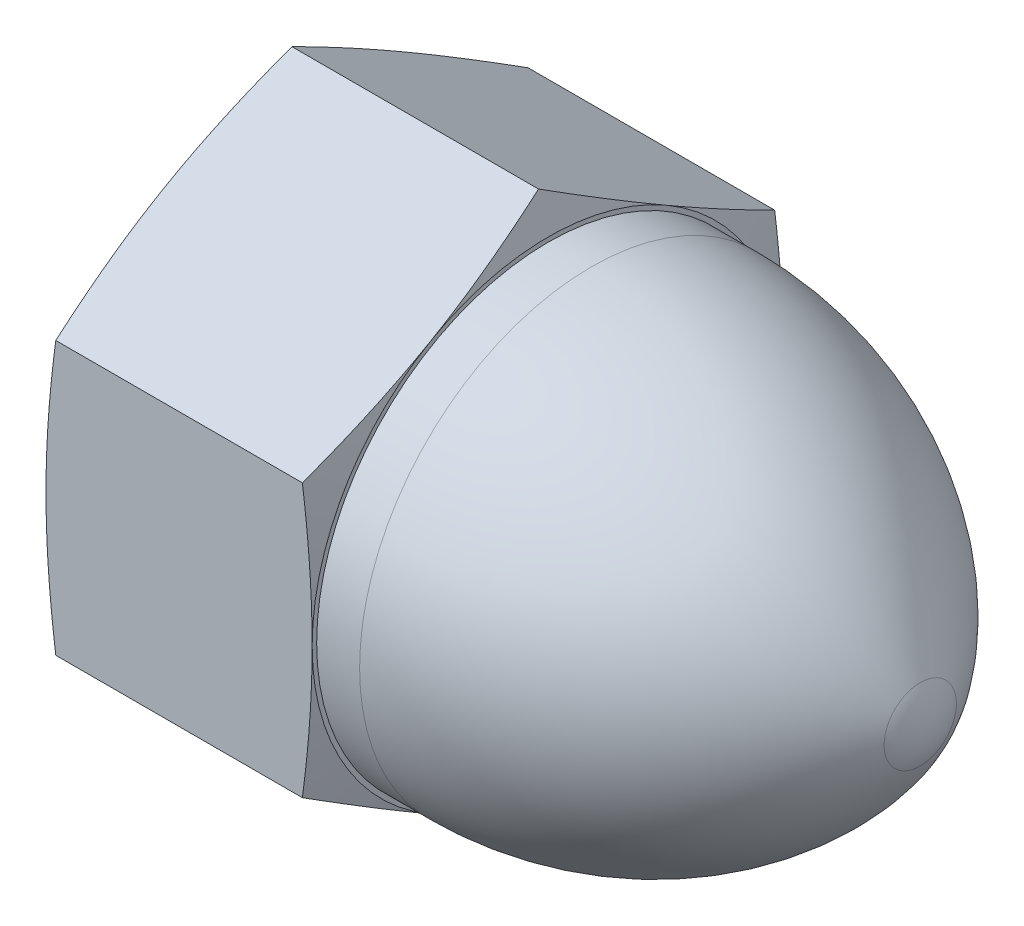
SolidWorks part; units mm, degrees
extrude "BaseNut" add sketch "BaseNutSke" along normal blind 20.574
sketch "BaseNutSke" plane through (0, 0, 0) normal (1, 0, 0) x (0, 0, -1)
  line L6 (18.2562, 10.5403) -> (18.2562, -10.5403)
  line L7 (-18.2562, 10.5403) -> (-18.2563, -10.5403)
  line L8 (18.2562, 10.5403) -> (0, 21.0805)
  line L9 (0, 21.0805) -> (-18.2562, 10.5403)
  line L10 (-18.2563, -10.5403) -> (0, -21.0805)
  line L11 (0, -21.0805) -> (18.2562, -10.5403)
  dimension "D1" = 120
  dimension "D2" = 18.2562
  dimension "D3" = 18.2562
  dimension "D4" = 60
revolve "DoubleChamfer" cut sketch "Sketch4" angle 360 about L10 other way angle 118
sketch "Sketch4" plane through (0, 0, 0) normal (0, 0, 1) x (1, 0, 0)
  line L0 (0, 18.2562) -> (1.9499, 25.5333)
  line L1 (20.574, 18.2562) -> (18.6245, 25.5333)
  line L2 (1.9499, 25.5333) -> (18.6245, 25.5333)
  line L3 (20.574, 18.2562) -> (33.274, 18.2562)
  line L4 (33.274, 18.2562) -> (33.274, 43.6562)
  line L5 (33.274, 43.6562) -> (-12.7, 43.6562)
  line L6 (0, 18.2562) -> (-12.7, 18.2562)
  line L7 (-12.7, 18.2562) -> (-12.7, 43.6562)
  line L8 (20.574, 21.0805) -> (20.574, 10.5403) construction
  line L9 (0, 21.0805) -> (0, 10.5403) construction
  line L10 (0, 0) -> (57.15, 0) construction
  point P17 (20.574, 18.2562)
  dimension "D1" = 14.997
  dimension "D2" = 15
  dimension "D3" = 12.7
  dimension "D4" = 12.7
  dimension "D5" = 18.1229
  dimension "D6" = 25.4
  dimension "D7" = 18.2562
ref_plane "Plane1" through (0, 0, 0) normal (0, 0, 1) x (1, 0, 0)
ref_plane "Plane2" through (0, 0, 0) normal (0, 1, 0) x (1, 0, 0)
ref_plane "Plane3" through (0, 0, 0) normal (1, 0, 0) x (0, 0, -1)
sketch "Sketch3" plane through (0, 0, 0) normal (0, 0, 1) x (1, 0, 0)
  line L0 (0, 0) -> (63.5, 0) construction
  line L1 (0, 10.5403) -> (0, -10.5403) construction
  line L2 (50.038, 0) -> (0, 0)
  line L3 (0, 17.907) -> (23.8939, 17.907)
  line L4 (0, -17.907) -> (22.225, -17.907) construction
  line L5 (0, 17.907) -> (0, 0)
  arc A0 (50.038, 0) -> (49.3273, 2.7926) centre (44.196, 0) ccw
  arc A1 (49.3273, 2.7926) -> (23.8939, 17.907) centre (23.8939, -11.049) ccw
  dimension "Nose_radius" = 5.842
  dimension "Body_radius" = 28.956
  dimension "Overall_ht" = 50.038
  dimension "Body_dia" = 35.814
revolve "Crown" add sketch "Sketch3" angle 360 about L0
sketch "Sketch5" plane through (0, 0, 0) normal (0, 0, 1) x (1, 0, 0)
  line L0 (0, 0) -> (44.45, 0) construction
  line L1 (0, 11.1125) -> (35.052, 11.1125)
  line L2 (0, 15.8104) -> (0, 0) construction
  line L3 (35.052, 11.1125) -> (41.7291, 0)
  line L4 (0, 0) -> (63.5, 0) construction
  line L5 (41.7291, 0) -> (0, 0)
  line L6 (0, 0) -> (0, 11.1125)
  line L7 (35.052, -11.1125) -> (41.7291, 0) construction
  line L8 (0, -11.1125) -> (35.052, -11.1125) construction
revolve "TapDrill" cut sketch "Sketch5"
cosmetic thread "ThreadCosmetic" [suppressed]
revolve "EndChamfer" cut sketch "EndChamferSketch" angle 360 about L4
sketch "EndChamferSketch" plane through (0, 0, 0) normal (0, 0, 1) x (1, 0, 0)
  line L0 (-0.0254, 12.7) -> (0.0254, 12.7)
  line L1 (0.0254, 12.7) -> (1.2481, 10.9537)
  line L2 (1.2481, 10.9537) -> (-0.0254, 10.9537)
  line L3 (-0.0254, 10.9537) -> (-0.0254, 12.7)
  line L4 (-3.175, 0) -> (-15.875, 0) construction
  dimension "D1" = 0.0508
  dimension "D2" = 35
  dimension "ChamferDepth" = 1.7463
  dimension "ThreadMajor" = 12.7
  dimension "D3" = 0.0254
sketch "ThdSchSke" plane through (0, 0, 0) normal (0, 1, 0) x (1, 0, 0)
  line L0 (0.0381, 12.7) -> (-1.0735, 11.1125)
  line L1 (-1.0735, 11.1125) -> (-1.0735, 4.2333)
  line L2 (-1.0735, 4.2333) -> (1.1497, 4.2333)
  line L3 (1.1497, 4.2333) -> (1.1497, 11.1125)
  line L4 (1.1497, 11.1125) -> (0.0381, 12.7)
  line L5 (-25.4, 0) -> (1.1497, 0) construction
  line L9 (3.2131, 3.175) -> (3.2131, -3.175) construction
  dimension "Tap_drill" = 22.225
  dimension "OverCut" = 8.4667
  dimension "Thread_major" = 25.4
  dimension "D1" = 0.0381
revolve "ThreadSchematic" [suppressed] cut sketch "ThdSchSke" angle 360 about L5
pattern_linear "ThdSchPat" [suppressed]
equation "\"D2@BaseNutSke\" = \"Width_flats@BaseNutSke\" / 2"
equation "\"D3@BaseNutSke\" = \"Width_flats@BaseNutSke\" / 2"
equation "\"D7@Sketch4\" = \"Width_flats@BaseNutSke\" / 2"
equation "\"Thread_major@ThdSchSke\" = \"Thread_nominal@ThreadCosmetic\""
equation "\"Tap_drill@ThdSchSke\" = \"Thread_min@Sketch5\""
equation "\"OverCut@ThdSchSke\" =  \"Thread_nominal@ThreadCosmetic\" / 3"
equation "\"Num_threads@ThdSchPat\" = int(  ( \"Hex_ht@BaseNut\" - 0.002 ) / \"Advance@ThdSchSke\" + 0.999 )  + 1"
equation "\"Advance@ThdSchPat\" = ( \"Hex_ht@BaseNut\" - 0.002 ) /  (\"Num_threads@ThdSchPat\" - 1) 'relax it"
equation "' \"Num_threads@ThdSchPat\" = \"Num_threads@ThdSchPat\" - sgn( \"Num_threads@ThdSchPat\" - 1) '---chamfered tips only---"
equation "\"ThreadMajor@EndChamferSketch\" = \"Thread_nominal@ThreadCosmetic\" * 0.5"
equation "\"ChamferDepth@EndChamferSketch\" = (\"Thread_nominal@ThreadCosmetic\" - \"Thread_min@Sketch5\") * 0.55"
